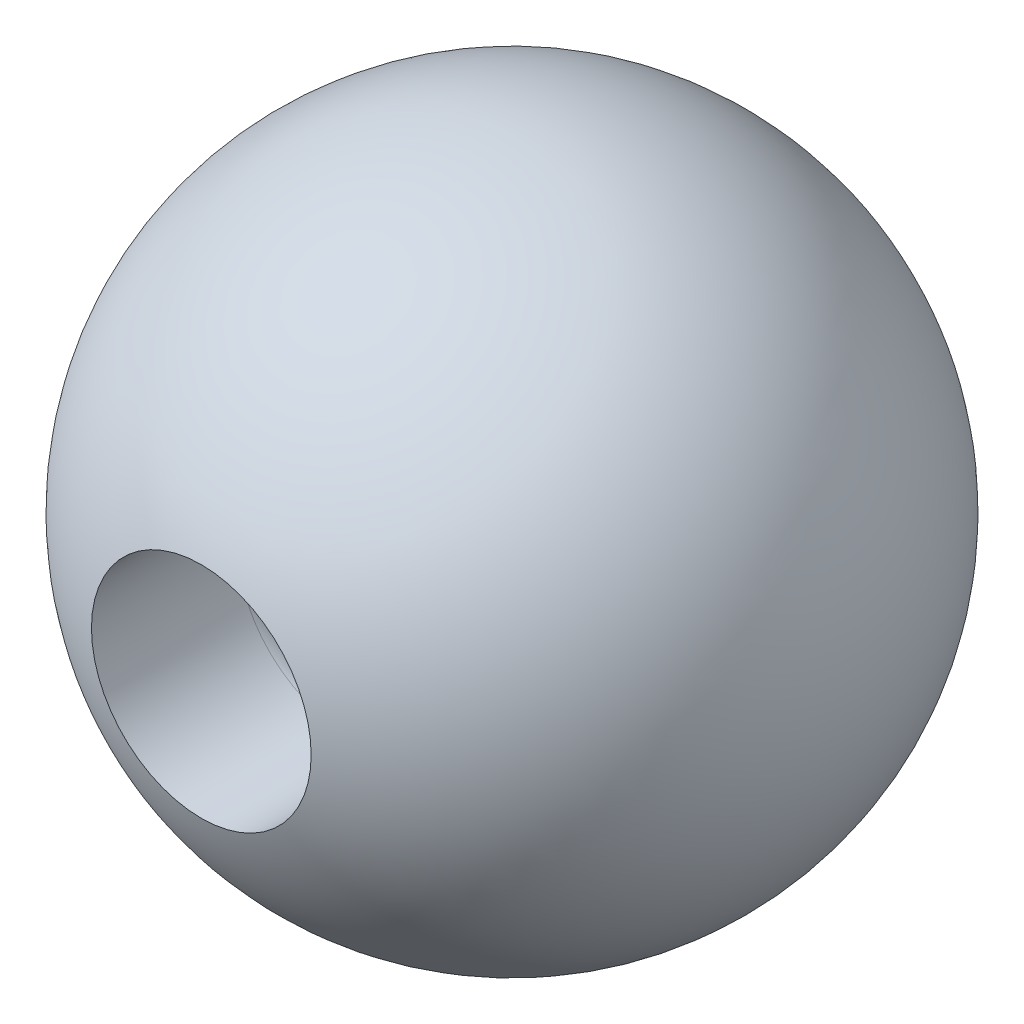
SolidWorks part; units mm, degrees
material "ABS"
ref_plane "Front Plane" through (0, 0, 0) normal (0, 0, 1) x (1, 0, 0)
ref_plane "Top Plane" through (0, 0, 0) normal (0, 1, 0) x (1, 0, 0)
ref_plane "Right Plane" through (0, 0, 0) normal (1, 0, 0) x (0, 0, -1)
sketch "Sketch1" plane through (0, 0, 0) normal (0, 1, 0) x (1, 0, 0)
  line L0 (0, 4.2689) -> (0, 0) construction
  line L1 (0, 1) -> (-0.5, 1)
  line L2 (-0.5, 1) -> (-0.5, 0.0858)
  line L3 (0, 3) -> (0, 1)
  arc A0 (0, 3) -> (-0.5, 0.0858) centre (0, 1.5) ccw
  dimension "D2" = 0.5
  dimension "D4" = 3
  dimension "D1" = 0.5
revolve "Revolve1" add sketch "Sketch1" angle 360 about L0
shell "Shell1" thickness 0.5 removed face at (-0.5, 0, -1)
fillet "Fillet1" radius 0.25 1 edges at (-0.5, 0, -1)
